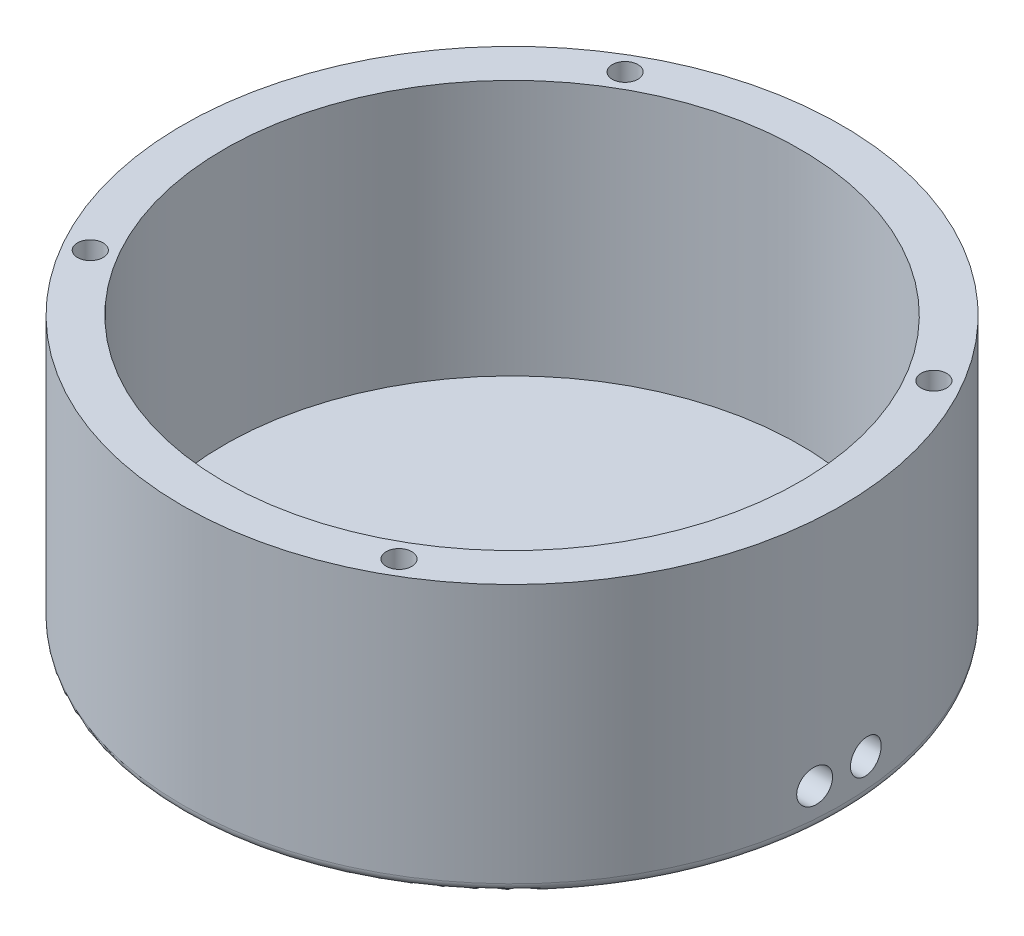
SolidWorks part; units mm, degrees
ref_plane "Front Plane" through (0, 0, 0) normal (0, 0, 1) x (1, 0, 0)
ref_plane "Top Plane" through (0, 0, 0) normal (0, 1, 0) x (1, 0, 0)
ref_plane "Right Plane" through (0, 0, 0) normal (1, 0, 0) x (0, 0, -1)
sketch "Sketch1" plane through (0, 0, 0) normal (0, 1, 0) x (1, 0, 0)
  circle A0 centre (0, 0) radius 51.5
  dimension "D1" = 103
extrude "Boss-Extrude1" add sketch "Sketch1" along normal blind 42
sketch "Sketch2" plane through (0, 42, 0) normal (0, 1, 0) x (1, 0, 0)
  circle A0 centre (0, 0) radius 45
  dimension "D1" = 90
extrude "Cut-Extrude1" cut sketch "Sketch2" against normal blind 40
fillet "Fillet1" radius 1.5 1 edges at (0, 0, 51.5)
sketch "Sketch3" plane through (0, 42, 0) normal (0, 1, 0) x (1, 0, 0)
  line L0 (0, 0) -> (0, 50) construction
  line L1 (0, 0) -> (43.3013, -25) construction
  line L2 (0, 0) -> (-43.3013, -25) construction
  circle A0 centre (0, 50) radius 1.5
  circle A1 centre (43.3013, -25) radius 1.5
  circle A2 centre (-43.3013, -25) radius 1.5
  dimension "D1" = 3
  dimension "D2" = 50
  dimension "D3" = 50
  dimension "D4" = 50
ref_plane "Plane1" through (52.5, 0, 0) normal (-1, 0, 0) x (0, 0, 1)
sketch "Sketch6" plane through (0, 42, 0) normal (0, 1, 0) x (1, 0, 0)
  line L1 (0, 0) -> (24.125, -41.7857) construction
  line L2 (0, 0) -> (41.7857, 24.125) construction
  line L3 (0, 0) -> (-24.125, 41.7857) construction
  line L4 (0, 0) -> (-41.7857, -24.125) construction
  line L8 (0, 0) -> (-43.3013, -25) construction
  circle A0 centre (41.7857, 24.125) radius 2
  circle A1 centre (-24.125, 41.7857) radius 2
  circle A2 centre (24.125, -41.7857) radius 2
  circle A3 centre (-41.7857, -24.125) radius 2
  dimension "D2" = 4
  dimension "D1" = 48.25
extrude "Cut-Extrude6" cut sketch "Sketch6" against normal blind 10
ref_plane "Plane2" through (47.5, 0, 0) normal (-1, 0, 0) x (0, 0, 1)
sketch "Sketch15" plane through (47.5, 0, 0) normal (-1, 0, 0) x (0, 0, 1)
  line L1 (0, 0) -> (0, 12) construction
  line L2 (0, 6) -> (-4, 6) construction
  line L3 (0, 6) -> (4, 6) construction
  circle A0 centre (-4, 6) radius 2.6
  circle A1 centre (4, 6) radius 2.6
  dimension "D1" = 4
  dimension "D4" = 5.2
  dimension "D5" = 5.2
  dimension "D2" = 4
  dimension "D3" = 12
extrude "Cut-Extrude12" cut sketch "Sketch15" along normal blind 15 and the other way blind 15
sketch "Sketch17" plane through (0, 2, 0) normal (0, 1, 0) x (1, 0, 0)
  circle A0 centre (0, 0) radius 6
extrude "Cut-Extrude13" cut sketch "Sketch17" against normal blind 1
sketch "Sketch18" plane through (0, 1, 0) normal (0, 1, 0) x (1, 0, 0)
  line L0 (-6, 0) -> (6, 0) construction
  line L1 (0, 6) -> (0, -6) construction
  line L2 (4.2426, -4.2426) -> (-4.2426, 4.2426) construction
  line L3 (-4.2426, -4.2426) -> (4.2426, 4.2426) construction
  line L4 (-3, -5.1962) -> (3, 5.1962) construction
  line L5 (-1.5529, -5.7956) -> (1.5529, 5.7956) construction
  line L6 (1.5529, -5.7956) -> (-1.5529, 5.7956) construction
  line L7 (3, -5.1962) -> (-3, 5.1962) construction
  line L8 (5.1962, -3) -> (-5.1962, 3) construction
  line L9 (5.7956, -1.5529) -> (-5.7956, 1.5529) construction
  line L10 (0, 0) -> (-5.7956, -1.5529) construction
  line L11 (-5.1962, -3) -> (5.1962, 3) construction
  line L12 (0, 0) -> (5.7956, 1.5529) construction
  circle A0 centre (0, 0) radius 6 construction
  circle A1 centre (0, 0) radius 6 construction
  circle A2 centre (-1.5, 0) radius 0.25
  circle A3 centre (-2.5, 0) radius 0.25
  circle A4 centre (-3.5, 0) radius 0.25
  circle A5 centre (-4.5, 0) radius 0.25
  circle A6 centre (-1.299, 0.75) radius 0.25
  circle A7 centre (-2.1651, 1.25) radius 0.25
  circle A8 centre (-3.0311, 1.75) radius 0.25
  circle A9 centre (-3.8971, 2.25) radius 0.25
  circle A10 centre (-0.75, 1.299) radius 0.25
  circle A11 centre (-1.25, 2.1651) radius 0.25
  circle A12 centre (-1.75, 3.0311) radius 0.25
  circle A13 centre (-2.25, 3.8971) radius 0.25
  circle A14 centre (0, 4.5) radius 0.25
  circle A15 centre (0, 3.5) radius 0.25
  circle A16 centre (0, 2.5) radius 0.25
  circle A17 centre (0, 1.5) radius 0.25
  circle A18 centre (0.75, 1.299) radius 0.25
  circle A19 centre (1.25, 2.1651) radius 0.25
  circle A20 centre (1.75, 3.0311) radius 0.25
  circle A21 centre (2.25, 3.8971) radius 0.25
  circle A22 centre (3.8971, 2.25) radius 0.25
  circle A23 centre (3.0311, 1.75) radius 0.25
  circle A24 centre (2.1651, 1.25) radius 0.25
  circle A25 centre (1.299, 0.75) radius 0.25
  circle A26 centre (4.5, 0) radius 0.25
  circle A27 centre (3.5, 0) radius 0.25
  circle A28 centre (2.5, 0) radius 0.25
  circle A29 centre (1.5, 0) radius 0.25
  circle A30 centre (3.8971, -2.25) radius 0.25
  circle A31 centre (3.0311, -1.75) radius 0.25
  circle A32 centre (2.1651, -1.25) radius 0.25
  circle A33 centre (1.299, -0.75) radius 0.25
  circle A34 centre (2.25, -3.8971) radius 0.25
  circle A35 centre (1.75, -3.0311) radius 0.25
  circle A36 centre (1.25, -2.1651) radius 0.25
  circle A37 centre (0.75, -1.299) radius 0.25
  circle A38 centre (0, -1.6) radius 0.25
  circle A39 centre (0, -2.5) radius 0.25
  circle A40 centre (0, -3.5) radius 0.25
  circle A41 centre (0, -4.5) radius 0.25
  circle A42 centre (-0.75, -1.299) radius 0.25
  circle A43 centre (-1.25, -2.1651) radius 0.25
  circle A44 centre (-1.75, -3.0311) radius 0.25
  circle A45 centre (-2.25, -3.8971) radius 0.25
  circle A46 centre (-1.299, -0.75) radius 0.25
  circle A47 centre (-2.1651, -1.25) radius 0.25
  circle A48 centre (-3.0311, -1.75) radius 0.25
  circle A49 centre (-3.8971, -2.25) radius 0.25
  circle A50 centre (0, 0) radius 0.5
  dimension "D13" = 0.5
  dimension "D14" = 0.5
  dimension "D61" = 1
  dimension "D1" = 15
  dimension "D2" = 15
  dimension "D3" = 15
  dimension "D4" = 15
  dimension "D5" = 15
  dimension "D6" = 15
  dimension "D7" = 15
  dimension "D8" = 15
  dimension "D9" = 15
  dimension "D10" = 15
  dimension "D11" = 1.5
  dimension "D12" = 4.5
  dimension "D15" = 1.5
  dimension "D16" = 1.5
  dimension "D17" = 1.5
  dimension "D18" = 1.5
  dimension "D19" = 1.5
  dimension "D20" = 1.5
  dimension "D21" = 1.5
  dimension "D22" = 1.5
  dimension "D23" = 1.5
  dimension "D24" = 1.6
  dimension "D25" = 1.5
  dimension "D26" = 2.5
  dimension "D27" = 2.5
  dimension "D28" = 2.5
  dimension "D29" = 2.5
  dimension "D30" = 2.5
  dimension "D31" = 2.5
  dimension "D32" = 2.5
  dimension "D33" = 2.5
  dimension "D34" = 2.5
  dimension "D35" = 2.5
  dimension "D36" = 2.5
  dimension "D37" = 2.5
  dimension "D38" = 3.5
  dimension "D39" = 3.5
  dimension "D40" = 3.5
  dimension "D41" = 3.5
  dimension "D42" = 3.5
  dimension "D43" = 3.5
  dimension "D44" = 3.5
  dimension "D45" = 3.5
  dimension "D46" = 3.5
  dimension "D47" = 3.5
  dimension "D48" = 3.5
  dimension "D49" = 3.5
  dimension "D50" = 4.5
  dimension "D51" = 4.5
  dimension "D52" = 4.5
  dimension "D53" = 4.5
  dimension "D54" = 4.5
  dimension "D55" = 4.5
  dimension "D56" = 4.5
  dimension "D57" = 4.5
  dimension "D58" = 4.5
  dimension "D59" = 4.5
  dimension "D60" = 4.5
extrude "Cut-Extrude14" cut sketch "Sketch18" against normal blind 1
